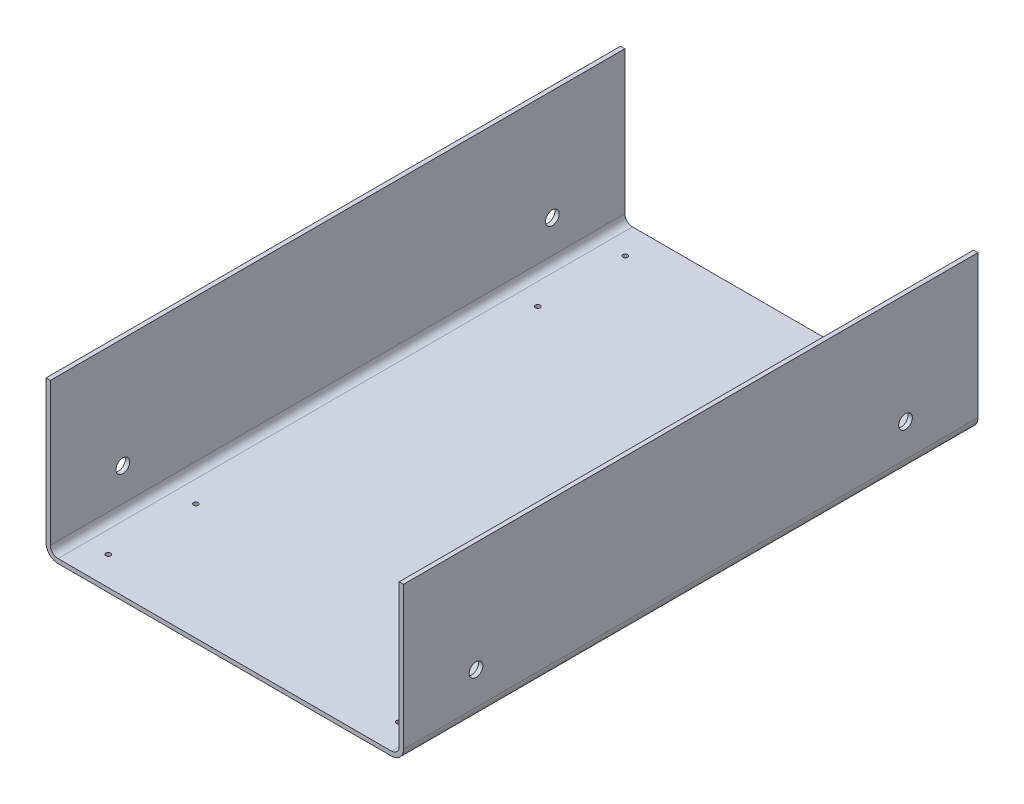
SolidWorks part; units mm, degrees
material "5052-H32"
ref_plane "Front Plane" through (0, 0, 0) normal (0, 0, 1) x (1, 0, 0)
ref_plane "Top Plane" through (0, 0, 0) normal (0, 1, 0) x (1, 0, 0)
ref_plane "Right Plane" through (0, 0, 0) normal (1, 0, 0) x (0, 0, -1)
sketch "Sketch1" plane through (0, 0, 0) normal (0, 0, 1) x (1, 0, 0)
  line L8 (127.5, 110) -> (127.5, 0)
  line L9 (-127.5, 0) -> (127.5, 0)
  line L10 (-127.5, 0) -> (-127.5, 110)
  line L11 (130.68, 110) -> (130.68, -3.18)
  line L12 (-130.68, -3.18) -> (130.68, -3.18)
  line L13 (-130.68, -3.18) -> (-130.68, 110)
  line L14 (127.5, 110) -> (130.68, 110)
  line L15 (-127.5, 110) -> (-130.68, 110)
  point P5 (0, 0)
  dimension "D1" = 255
  dimension "D2" = 110
  dimension "D3" = 3.18
extrude "Boss-Extrude1" add sketch "Sketch1" along normal blind 420
fillet "Inside Fillet" radius 5.56 2 edges at (127.5, 0, 210) (-127.5, 0, 210)
fillet "Outside Fillet" radius 8.73 2 edges at (-130.68, -3.18, 210) (130.68, -3.18, 210)
sketch "Sketch2" plane through (130.68, 0, 0) normal (1, 0, 0) x (0, 0, -1)
  line L0 (-420, 5.55) -> (-420, 110) construction
  line L2 (0, 5.55) -> (0, 110) construction
  line L4 (-367, 29.5) -> (-367, 0) construction
  line L7 (-53, 29.5) -> (-53, 0) construction
  circle A0 centre (-367, 29.5) radius 5
  circle A1 centre (-53, 29.5) radius 5
  dimension "D3" = 10
  dimension "D4" = 10
  dimension "D1" = 53
  dimension "D2" = 29.5
  dimension "D5" = 53
  dimension "D6" = 29.5
extrude "Bearing Holes" cut sketch "Sketch2" against normal up to surface (261.36 mm away) up to face at (-130.68, 57.775, 210)
sketch "Sketch3" plane through (0, 0, 0) normal (0, 1, 0) x (1, 0, 0)
  line L0 (-106.15, -335) -> (-106.15, -399) construction
  line L1 (121.94, -420) -> (-121.94, -420) construction
  line L2 (-127.5, -420) -> (-127.5, 0) construction
  line L3 (-130.68, -210) -> (130.68, -210) construction
  line L4 (-130.68, -420) -> (-130.68, 0) construction
  line L5 (130.68, -420) -> (130.68, 0) construction
  line L6 (0, -420) -> (0, -210) construction
  line L7 (-106.15, -85) -> (-106.15, -21) construction
  line L8 (121.94, 0) -> (-121.94, 0) construction
  line L9 (106.15, -335) -> (106.15, -399) construction
  line L10 (106.15, -85) -> (106.15, -21) construction
  circle A0 centre (-106.15, -335) radius 1.7526
  circle A1 centre (-106.15, -399) radius 1.7526
  circle A6 centre (106.15, -399) radius 1.7526
  circle A7 centre (106.15, -335) radius 1.7526
  circle A8 centre (-106.15, -85) radius 1.7526
  circle A9 centre (-106.15, -21) radius 1.7526
  circle A10 centre (106.15, -21) radius 1.7526
  circle A11 centre (106.15, -85) radius 1.7526
  point P4 (-106.15, -367)
  point P23 (-106.15, -53)
  dimension "D4" = 3.5052
  dimension "D5" = 3.5052
  dimension "D6" = 3.5052
  dimension "D7" = 3.5052
  dimension "D1" = 64
  dimension "D2" = 53
  dimension "D3" = 21.35
  dimension "D8" = 64
  dimension "D9" = 21.35
  dimension "D10" = 53
extrude "Motor Mount Holes" cut sketch "Sketch3" against normal up to next
equation "\"W\"= 255mm"
equation "\"L\"= 420mm"
equation "\"Offset\"= 18mm"
equation "\"H\"= 110mm"
equation "\"T\"= 4.7625 * 2 / 3mm"
equation "\"Inside Fillet Radius\"= 5.55625mm"
equation "\"Hole\"=25mm"
equation "\"D1@Boss-Extrude1\"=\"L\""
equation "\"Compartment Width1\"= 90mm"
equation "\"Compartment Width2\"= 90mm"
equation "\"D1@Sketch1\"=\"W\""
equation "\"D2@Sketch1\"=\"H\""
equation "\"D3@Sketch1\"=\"T\""
equation "\"D1@Inside Fillet\"=\"Inside Fillet Radius\""
equation "\"D1@Outside Fillet\"=\"Inside Fillet Radius\"+\"T\""
equation "\"D2@Sketch3\"=53"
